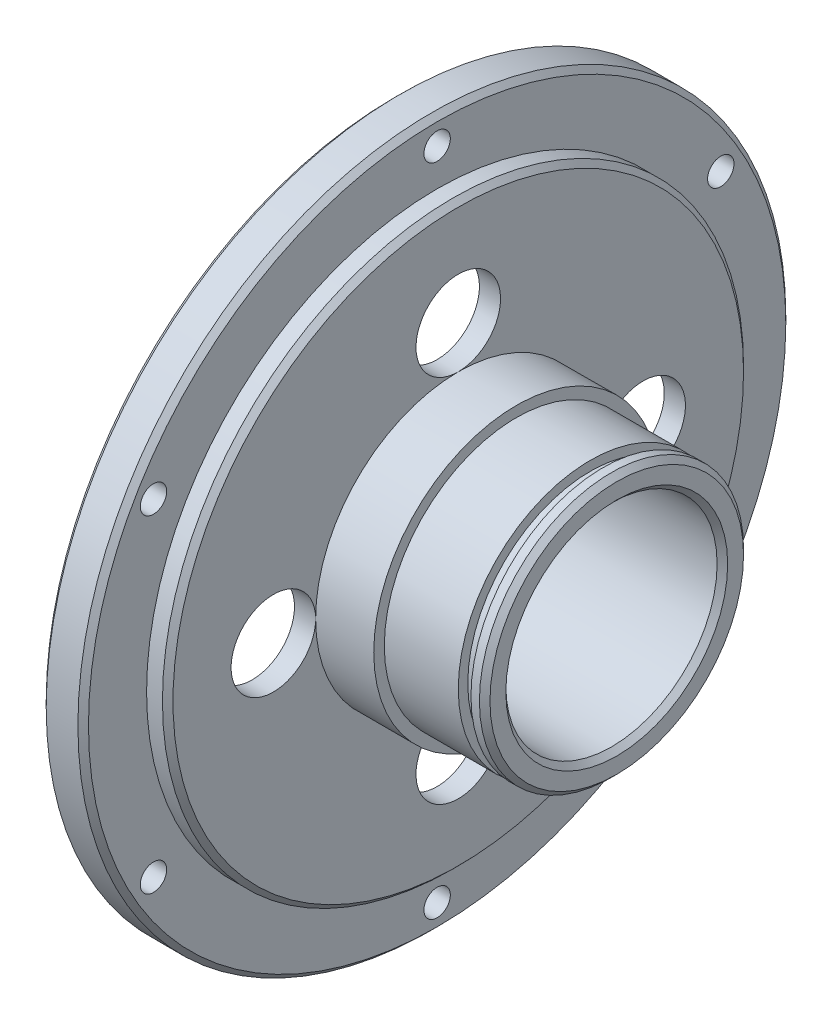
SolidWorks part; units mm, degrees
ref_plane "前视基准面" through (0, 0, 0) normal (0, 0, 1) x (1, 0, 0)
ref_plane "上视基准面" through (0, 0, 0) normal (0, 1, 0) x (1, 0, 0)
ref_plane "右视基准面" through (0, 0, 0) normal (1, 0, 0) x (0, 0, -1)
other "Configuration Table"
sketch "草图1" plane through (0, 0, 0) normal (0, 0, 1) x (1, 0, 0)
  line L0 (0, 0) -> (30511.7652, 0) construction
  line L1 (0, 33.5) -> (4, 33.5)
  line L2 (4, 33.5) -> (4, 27.5)
  line L3 (4, 27.5) -> (6, 27.5)
  line L4 (6, 27.5) -> (6, 13.5)
  line L5 (6, 13.5) -> (11.5, 13.5)
  line L6 (11.5, 13.5) -> (11.5, 12.5)
  line L7 (11.5, 12.5) -> (21, 12.5)
  line L8 (21, 12.5) -> (21, 10)
  line L9 (21, 10) -> (6, 10)
  line L10 (6, 10) -> (6, 9)
  line L11 (6, 9) -> (4, 9)
  line L12 (4, 9) -> (4, 25.5)
  line L13 (4, 25.5) -> (0, 25.5)
  line L14 (0, 25.5) -> (0, 33.5)
  line L16 (18.5, 12.5) -> (19.7, 12.5)
  line L17 (18.5, 12.5) -> (18.5, 11.6)
  line L18 (18.5, 11.6) -> (19.7, 11.6)
  line L19 (19.7, 12.5) -> (19.7, 11.6)
  dimension "D1" = 51
  dimension "D2" = 55
  dimension "D3" = 67
  dimension "D4" = 27
  dimension "D5" = 25
  dimension "D6" = 18
  dimension "D7" = 20
  dimension "D8" = 4
  dimension "D9" = 4
  dimension "D10" = 2
  dimension "D11" = 9.5
  dimension "D12" = 5.5
  dimension "D13" = 1.3
  dimension "D14" = 23.2
  dimension "D15" = 1.2
revolve "旋转1" add sketch "草图1" angle 360 about L0 region at (2, 33.1773, 0)
chamfer "倒角1" distance 0.5 angle 45 7 edges at (0, 0, 33.5) (4, 0, 33.5) (6, 0, 27.5) (21, 0, 12.5) (21, 0, 10) (4, 0, 25.5) (0, 0, 25.5)
sketch "草图2" plane through (6, 0, 0) normal (1, 0, 0) x (0, 0, -1)
  circle A0 centre (0, 0) radius 17.5 construction
  circle A1 centre (0, 17.5) radius 4
  dimension "D1" = 35
  dimension "D2" = 8
extrude "切除-拉伸1" cut sketch "草图2" against normal through all both and the other way through all
pattern_circular "阵列(圆周)1" count 4 over 360 about axis through (0, 0, 0) along (-1, 0, 0) of "切除-拉伸1" reverse direction yes
hole_wizard "M3 螺纹孔1" positions "草图3" profile "草图4" tap size "M3" standard "GB" end condition through all
sketch "草图3" plane through (4, 0, 0) normal (1, 0, 0) x (0, 0, -1)
  point P0 (0, 31)
  dimension "D1" = 31
sketch "草图4" plane through (4, 31, 0) normal (0, 1, 0) x (0, 0, -1)
  line L0 (0, 0) -> (0, 4)
  line L1 (0, 4) -> (1.25, 4)
  line L2 (1.25, 4) -> (1.25, 0)
  line L5 (1.25, 0) -> (0, 0)
  line L11 (0, -6.35) -> (0, 107.95) construction
  dimension "通孔螺纹孔钻头直径" = 2.5
  dimension "通孔螺纹孔钻头深度" = 4
cosmetic thread "孔螺蚊线1" parameters "D2"=3
pattern_circular "阵列(圆周)2" count 6 over 360 about axis through (0, 0, 0) along (-1, 0, 0) of "M3 螺纹孔1"
